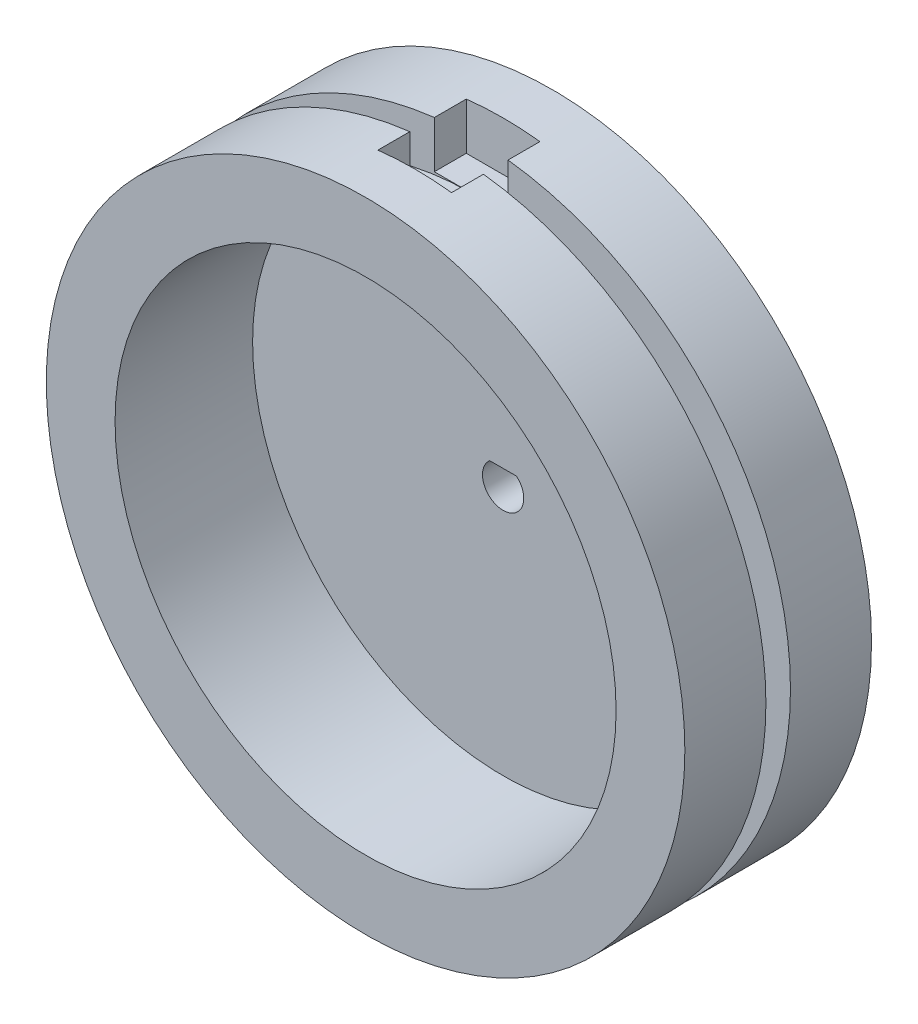
SolidWorks part; units mm, degrees
ref_plane "Front Plane" through (0, 0, 0) normal (0, 0, 1) x (1, 0, 0)
ref_plane "Top Plane" through (0, 0, 0) normal (0, 1, 0) x (1, 0, 0)
ref_plane "Right Plane" through (0, 0, 0) normal (1, 0, 0) x (0, 0, -1)
sketch "Sketch2" plane through (0, 0, 0) normal (1, 0, 0) x (0, 0, -1)
  line L0 (0, 0) -> (0, 32.5)
  line L1 (0, 32.5) -> (-8.25, 32.5)
  line L2 (-19, 32.5) -> (-19, 25.5)
  line L3 (-19, 25.5) -> (-5, 25.5)
  line L4 (-5, 25.5) -> (-5, 0)
  line L5 (-5, 0) -> (0, 0)
  line L6 (-8.25, 32.5) -> (-8.25, 27.5)
  line L7 (-8.25, 27.5) -> (-10.75, 27.5)
  line L8 (-10.75, 27.5) -> (-10.75, 32.5)
  line L9 (-10.75, 32.5) -> (-19, 32.5)
  dimension "D1" = 19
  dimension "D2" = 32.5
  dimension "D3" = 7
  dimension "D4" = 5
  dimension "D5" = 2.5
  dimension "D6" = 8.25
  dimension "D7" = 5
revolve "Revolve1" add sketch "Sketch2" angle 360 about L5
ref_plane "Plane1" through (0, 32.5, 0) normal (0, 1, 0) x (1, 0, 0)
sketch "Sketch7" plane through (0, 32.5, 0) normal (0, 1, 0) x (1, 0, 0)
  line L1 (-3.75, -14) -> (3.75, -14)
  line L2 (-3.75, -14) -> (-3.75, -5)
  line L3 (-3.75, -5) -> (3.75, -5)
  line L4 (3.75, -14) -> (3.75, -5)
  line L5 (-3.75, -9.5) -> (3.75, -9.5) construction
  line L6 (32.5, 0) -> (-32.5, 0) construction
  line L7 (0, -5) -> (0, 0) construction
  dimension "D1" = 9.5
  dimension "D2" = 9
  dimension "D3" = 7.5
extrude "Cut-Extrude1" cut sketch "Sketch7" against normal blind 5
mirror "Mirror1" about plane through (0, 0, 0) normal (0, 1, 0) of "Cut-Extrude1"
sketch "Sketch8" plane through (0, 0, 0) normal (0, 0, -1) x (-1, 0, 0)
  line L0 (-1.3601, 1.6) -> (1.3601, 1.6)
  arc A0 (-1.3601, 1.6) -> (1.3601, 1.6) centre (0, 0) ccw
  dimension "D1" = 4.2
  dimension "D2" = 1.6
extrude "Shaft Hole" cut sketch "Sketch8" against normal through all
